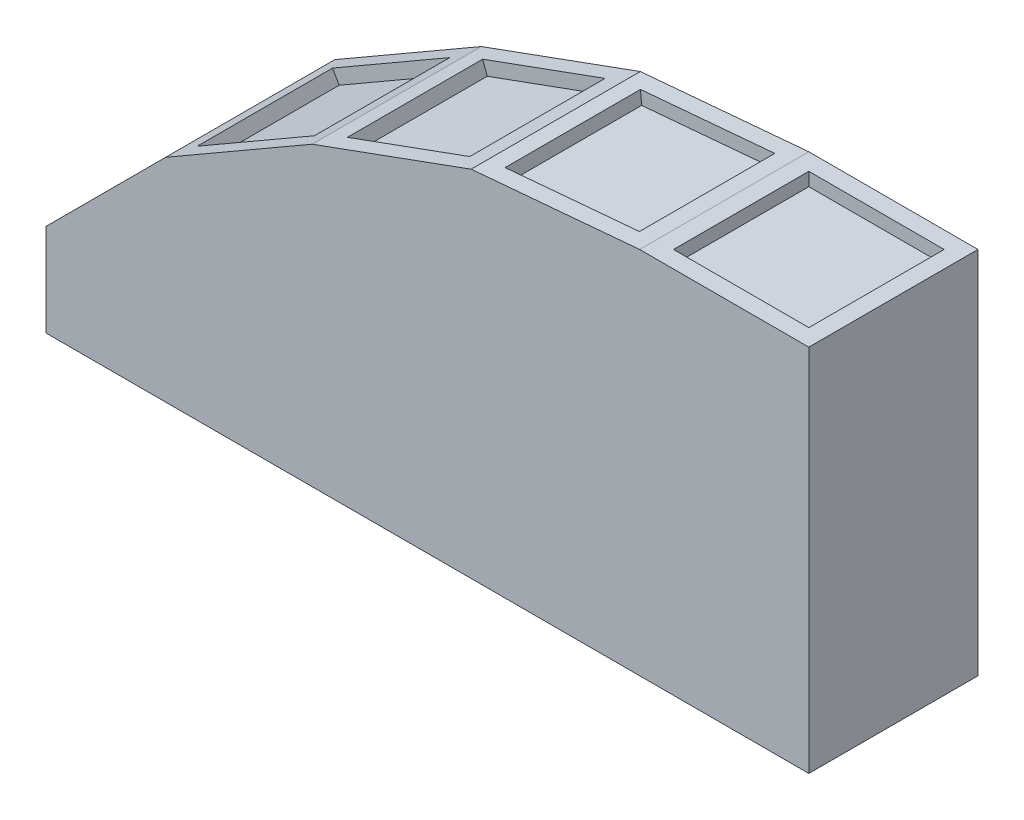
SolidWorks part; units mm, degrees
ref_plane "Front Plane" through (0, 0, 0) normal (0, 0, 1) x (1, 0, 0)
ref_plane "Top Plane" through (0, 0, 0) normal (0, 1, 0) x (1, 0, 0)
ref_plane "Right Plane" through (0, 0, 0) normal (1, 0, 0) x (0, 0, -1)
sketch "Sketch1" plane through (0, 0, 0) normal (0, 1, 0) x (1, 0, 0)
  line L1 (0, 0) -> (127, 0)
  line L2 (0, 0) -> (0, 127)
  line L3 (0, 127) -> (127, 127)
  line L4 (127, 0) -> (127, 127)
  line L5 (12.7, 114.3) -> (114.3, 114.3)
  line L6 (12.7, 114.3) -> (12.7, 12.7)
  line L7 (12.7, 12.7) -> (114.3, 12.7)
  line L8 (114.3, 114.3) -> (114.3, 12.7)
  dimension "D1" = 101.6
  dimension "D2" = 101.6
  dimension "D3" = 12.7
  dimension "D4" = 12.7
  dimension "D5" = 12.7
  dimension "D6" = 12.7
extrude "Boss-Extrude1" add sketch "Sketch1" along normal blind 10
ref_plane "Plane1" through (-0.8682, 9.924, 0) normal (-0.0872, 0.9962, 0) x (0, 0, 1)
sketch "Sketch18" plane through (-0.8682, 9.924, 0) normal (-0.0872, 0.9962, 0) x (0, 0, 1)
  line L1 (-127, 0.8716) -> (0, 0.8716)
  line L2 (-127, 0.8716) -> (-127, -126.1284)
  line L3 (-127, -126.1284) -> (0, -126.1284)
  line L4 (0, 0.8716) -> (0, -126.1284)
  dimension "D1" = 127
  dimension "D2" = 127
extrude "Boss-Extrude17" add sketch "Sketch18" against normal blind 10
ref_plane "Plane8" through (-14.4561, 39.7179, 0) normal (-0.342, 0.9397, 0) x (0, 0, 1)
sketch "Sketch20" plane through (-14.4561, 39.7179, 0) normal (-0.342, 0.9397, 0) x (0, 0, 1)
  line L1 (-127, -119.2524) -> (0, -119.2524)
  line L2 (-127, -119.2524) -> (-127, -246.2524)
  line L3 (-127, -246.2524) -> (0, -246.2524)
  line L4 (0, -119.2524) -> (0, -246.2524)
  dimension "D1" = 127
  dimension "D2" = 127
extrude "Boss-Extrude19" add sketch "Sketch20" against normal blind 10
sketch "Sketch21" plane through (-0.8682, 9.924, 0) normal (-0.0872, 0.9962, 0) x (0.9962, 0.0872, 0)
  line L0 (114.7366, 114.3) -> (13.5232, 114.3) construction
  line L1 (-113.2351, 114.3) -> (-12.0218, 114.3)
  line L2 (-113.2351, 114.3) -> (-113.2351, 12.7)
  line L3 (-113.2351, 12.7) -> (-12.0218, 12.7)
  line L4 (-12.0218, 114.3) -> (-12.0218, 12.7)
  line L5 (13.5232, 114.3) -> (13.5232, 12.7) construction
  line L6 (0.8716, 127) -> (-126.1284, 127) construction
  line L7 (-126.1284, 127) -> (-126.1284, 0) construction
  point P10 (-62.6284, 127)
  point P11 (-62.6284, 114.3)
  point P14 (-126.1284, 63.5)
  point P15 (-113.2351, 63.5)
extrude "Cut-Extrude1" cut sketch "Sketch21" against normal blind 10
sketch "Sketch22" plane through (-14.4561, 39.7179, 0) normal (-0.342, 0.9397, 0) x (0.9397, 0.342, 0)
  line L0 (-246.2524, 127) -> (-246.2524, 0) construction
  line L1 (-231.6347, 114.3) -> (-133.8701, 114.3)
  line L2 (-231.6347, 114.3) -> (-231.6347, 12.7)
  line L3 (-231.6347, 12.7) -> (-133.8701, 12.7)
  line L4 (-133.8701, 114.3) -> (-133.8701, 12.7)
  line L5 (-119.2524, 127) -> (-246.2524, 127) construction
  line L6 (-9.0338, 114.3) -> (-106.7984, 114.3) construction
  line L7 (-106.7984, 114.3) -> (-106.7984, 12.7) construction
  point P6 (-246.2524, 63.5)
  point P7 (-231.6347, 63.5)
  point P10 (-182.7524, 127)
  point P11 (-182.7524, 114.3)
extrude "Cut-Extrude2" cut sketch "Sketch22" against normal blind 10
sketch "Sketch23" plane through (0, 0, 0) normal (0, -1, 0) x (1, 0, 0)
  line L1 (0, 0) -> (127, 0)
  line L2 (0, 0) -> (0, -127)
  line L3 (0, -127) -> (127, -127)
  line L4 (127, 0) -> (127, -127)
extrude "Boss-Extrude21" add sketch "Sketch23" along normal blind 10
sketch "Sketch24" plane through (0.0033, -0.0379, 0) normal (0.0872, -0.9962, 0) x (0.9962, 0.0872, 0)
  line L0 (-124.8119, 0) -> (-0.0033, 0) construction
  line L1 (-124.8119, 0) -> (2.1881, 0)
  line L2 (-124.8119, 0) -> (-124.8119, -127)
  line L3 (-124.8119, -127) -> (2.1881, -127)
  line L4 (2.1881, 0) -> (2.1881, -127)
  line L5 (-0.0033, -127) -> (-124.8119, -127) construction
  point P4 (-0.8716, 0)
  point P9 (-0.8716, 0)
  point P10 (-0.8716, -127)
  point P11 (-0.0033, -127)
  dimension "D1" = 127
extrude "Boss-Extrude24" add sketch "Sketch24" along normal blind 10
sketch "Sketch25" plane through (-11.0359, 30.321, 0) normal (0.342, -0.9397, 0) x (0.9397, 0.342, 0)
  line L0 (-246.2524, -127) -> (-246.2524, 0) construction
  line L1 (-246.2524, 0) -> (-119.2524, 0)
  line L2 (-246.2524, 0) -> (-246.2524, -127)
  line L3 (-246.2524, -127) -> (-119.2524, -127)
  line L4 (-119.2524, 0) -> (-119.2524, -127)
  point P6 (0, 0)
  dimension "D1" = 127
  dimension "D2" = 127
extrude "Boss-Extrude25" add sketch "Sketch25" along normal blind 10
ref_plane "Plane9" through (-42.193, 73.0805, 0) normal (-0.5, 0.866, 0) x (0, 0, 1)
sketch "Sketch26" plane through (-42.193, 73.0805, 0) normal (-0.5, 0.866, 0) x (0, 0, 1)
  line L1 (-127, -235.1717) -> (0, -235.1717)
  line L2 (-127, -235.1717) -> (-127, -362.1717)
  line L3 (-127, -362.1717) -> (0, -362.1717)
  line L4 (0, -235.1717) -> (0, -362.1717)
  dimension "D1" = 127
  dimension "D2" = 127
extrude "Boss-Extrude26" add sketch "Sketch26" against normal blind 10
sketch "Sketch27" plane through (-42.193, 73.0805, 0) normal (-0.5, 0.866, 0) x (0.866, 0.5, 0)
  line L0 (-235.1717, 127) -> (-362.1717, 127) construction
  line L1 (-349.4717, 114.3) -> (-247.8717, 114.3)
  line L2 (-349.4717, 114.3) -> (-349.4717, 12.7)
  line L3 (-349.4717, 12.7) -> (-247.8717, 12.7)
  line L4 (-247.8717, 114.3) -> (-247.8717, 12.7)
  line L5 (-362.1717, 127) -> (-362.1717, 0) construction
  point P6 (-298.6717, 127)
  point P7 (-298.6717, 114.3)
  point P10 (-362.1717, 63.5)
  point P11 (-349.4717, 63.5)
  dimension "D1" = 101.6
  dimension "D2" = 101.6
extrude "Cut-Extrude3" cut sketch "Sketch27" against normal blind 10
sketch "Sketch28" plane through (-37.193, 64.4202, 0) normal (0.5, -0.866, 0) x (0.866, 0.5, 0)
  line L1 (-362.1717, 0) -> (-235.1717, 0)
  line L2 (-362.1717, 0) -> (-362.1717, -127)
  line L3 (-362.1717, -127) -> (-235.1717, -127)
  line L4 (-235.1717, 0) -> (-235.1717, -127)
  dimension "D1" = 127
  dimension "D2" = 127
extrude "Boss-Extrude27" add sketch "Sketch28" along normal blind 10
ref_plane "Plane10" through (-123.9188, 123.9188, 0) normal (-0.7071, 0.7071, 0) x (0, 0, 1)
sketch "Sketch29" plane through (-123.9188, 123.9188, 0) normal (-0.7071, 0.7071, 0) x (0, 0, 1)
  line L1 (-127, -327.9902) -> (0, -327.9902)
  line L2 (-127, -327.9902) -> (-127, -454.9902)
  line L3 (-127, -454.9902) -> (0, -454.9902)
  line L4 (0, -327.9902) -> (0, -454.9902)
  dimension "D1" = 127
  dimension "D2" = 127
extrude "Boss-Extrude28" add sketch "Sketch29" against normal blind 10
sketch "Sketch30" plane through (-123.9188, 123.9188, 0) normal (-0.7071, 0.7071, 0) x (0, 0, 1)
  line L0 (-127, -454.9902) -> (0, -454.9902) construction
  line L1 (-114.3, -340.6902) -> (-12.7, -340.6902)
  line L2 (-114.3, -340.6902) -> (-114.3, -442.2902)
  line L3 (-114.3, -442.2902) -> (-12.7, -442.2902)
  line L4 (-12.7, -340.6902) -> (-12.7, -442.2902)
  line L5 (-127, -327.9902) -> (-127, -454.9902) construction
  point P6 (-63.5, -454.9902)
  point P7 (-63.5, -442.2902)
  point P10 (-127, -391.4902)
  point P11 (-114.3, -391.4902)
  dimension "D1" = 101.6
  dimension "D2" = 101.6
extrude "Cut-Extrude4" cut sketch "Sketch30" against normal blind 10
sketch "Sketch31" plane through (-116.8477, 116.8477, 0) normal (0.7071, -0.7071, 0) x (0, 0, -1)
  line L1 (0, -454.9902) -> (127, -454.9902)
  line L2 (0, -454.9902) -> (0, -327.9902)
  line L3 (0, -327.9902) -> (127, -327.9902)
  line L4 (127, -454.9902) -> (127, -327.9902)
  dimension "D1" = 127
  dimension "D2" = 127
extrude "Boss-Extrude29" add sketch "Sketch31" along normal blind 10
sketch "Sketch32" plane through (0, 0, 0) normal (0, 0, 1) x (1, 0, 0)
  line L1 (127, -241.7679) -> (127, -10)
  line L2 (127, -10) -> (0.8732, -10)
  line L3 (0.8732, -10) -> (-122.1506, -20.7632)
  line L4 (-122.1506, -20.7632) -> (-237.373, -62.7007)
  line L5 (-237.373, -62.7007) -> (-343.5626, -124.0093)
  line L6 (-343.5626, -124.0093) -> (-431.5033, -211.95)
  line L10 (127, -241.7679) -> (127, -267.1679)
  line L11 (127, -267.1679) -> (-445.6455, -267.1679)
  line L12 (-445.6455, -267.1679) -> (-445.6455, -197.8079)
  line L13 (-445.6455, -197.8079) -> (-431.5033, -211.95)
  dimension "D1" = 25.4
extrude "Boss-Extrude30" add sketch "Sketch32" against normal up to surface (127 mm away) up to face at (-171.1316, -64.2342, -127)
sketch "Sketch33" plane through (0, 0, -127) normal (0, 0, -1) x (-1, 0, 0)
  line L0 (-127, 10) -> (-127, -267.1679) construction
  line L1 (-127, 10) -> (0, 10) construction
  line L2 (0, 10) -> (126.5167, -1.0688) construction
  line L3 (126.5167, -1.0688) -> (245.8577, -44.5053) construction
  line L4 (245.8577, -44.5053) -> (355.8429, -108.0053) construction
  line L5 (355.8429, -108.0053) -> (445.6455, -197.8079) construction
  text T0 "0"
  text T1 "5"
  text T2 "15\r\n"
  text T3 "30\r\n"
  text T4 "45\r\n"
  point P1 (-41.7045, -5.1104)
  dimension "D1" = 63.5
  dimension "D2" = 12.7
  dimension "D3" = 12.7
  dimension "D4" = 190.5
  dimension "D5" = 12.7
  dimension "D6" = 317.5
  dimension "D7" = 12.7
  dimension "D8" = 419.1
  dimension "D9" = 12.7
  dimension "D10" = 520.7
extrude "Cut-Extrude5" cut sketch "Sketch33" against normal blind 6.35
sketch "Sketch34" plane through (0, 0, -127) normal (0, 0, -1) x (-1, 0, 0)
  line L0 (0, 10) -> (126.5167, -1.0688) construction
  line L2 (-127, 10) -> (-127, -267.1679) construction
  text T0 "5"
  point P1 (71.4797, -5.7239)
  point P6 (-127, -9.4019)
  dimension "D1" = 12.7
  dimension "D2" = 190.5
